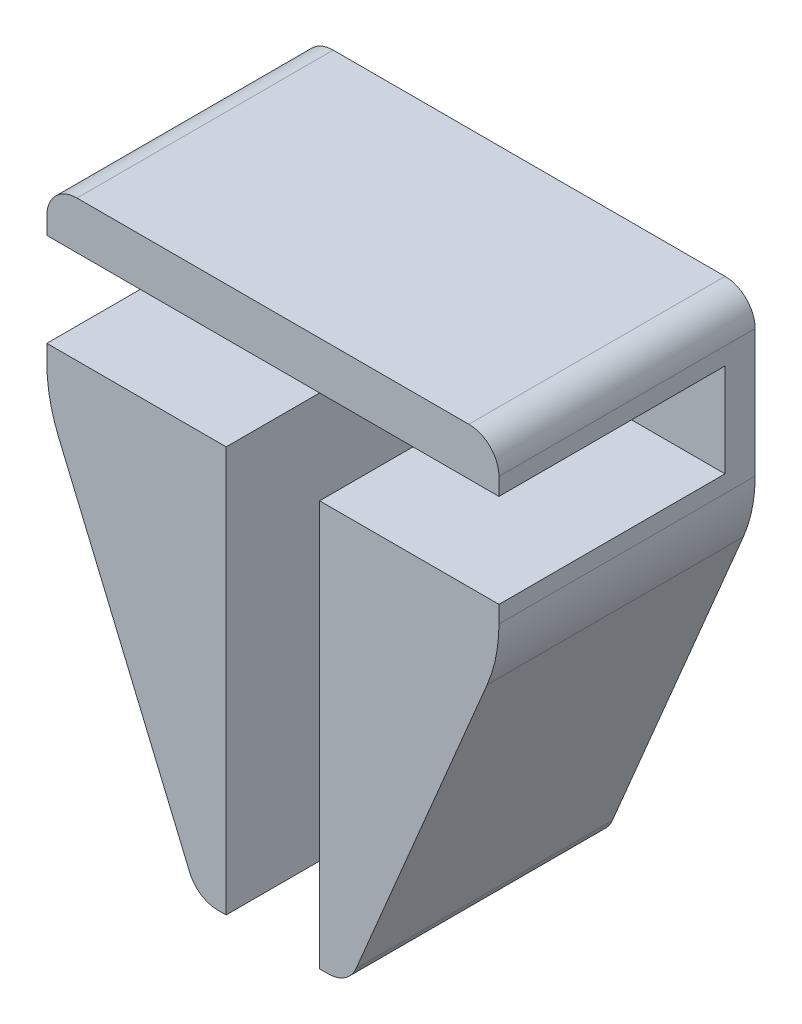
SolidWorks part; units mm, degrees
ref_plane "Płaszczyzna przednia" through (0, 0, 0) normal (0, 0, 1) x (1, 0, 0)
ref_plane "Płaszczyzna górna" through (0, 0, 0) normal (0, 1, 0) x (1, 0, 0)
ref_plane "Płaszczyzna prawa" through (0, 0, 0) normal (1, 0, 0) x (0, 0, -1)
sketch "Szkic1" plane through (0, 0, 0) normal (0, 0, 1) x (1, 0, 0)
  line L0 (-15, 0) -> (15, 0) construction
  line L1 (0, 0) -> (0, -30) construction
  line L2 (-5, -30) -> (5, -30)
  line L3 (15, 6.25) -> (15, -6.25)
  line L4 (-15, 6.25) -> (-15, -6.25)
  line L5 (-15, -6.25) -> (-5, -30)
  line L6 (5, -30) -> (15, -6.25)
  line L7 (15, 6.25) -> (-15, 6.25)
  line L8 (-15, -3.1) -> (-3.1, -3.1)
  line L9 (-15, 3.1) -> (15, 3.1)
  line L10 (-3.1, -3.1) -> (-3.1, -30)
  line L11 (3.1, -3.1) -> (3.1, -30)
  line L12 (3.1, 0) -> (3.1, -30) construction
  line L13 (3.1, -3.1) -> (15, -3.1)
  line L14 (-15, -3.1) -> (15, -3.1) construction
  line L15 (-3.1, 0) -> (-3.1, -30) construction
  point P4 (0, 0)
  point P10 (0, -30)
  point P13 (15, 0)
  point P15 (-15, 0)
  dimension "D1" = 30
  dimension "D2" = 30
  dimension "D3" = 12.5
  dimension "D4" = 10
  dimension "D5" = 3.1
  dimension "D6" = 3.1
  dimension "D7" = 3.1
  dimension "D8" = 3.1
extrude "Dodanie-wyciągnięcie1" add sketch "Szkic1" along normal blind 15 contours L4 L9 L3 L7 | L10 L8 L4 L5 L2 | L13 L11 L2 L6 L3 region at (-7.5068, -13.2868, 0) region at (7.5068, -13.2868, 0) region at (0, 4.675, 0)
extrude "Dodanie-wyciągnięcie2" add sketch "Szkic1<3>" against normal blind 2 contours L7 L4 L5 L2 L6 L3
sketch "Szkic1<3>" plane through (0, 0, 0) normal (0, 0, 1) x (1, 0, 0) same geometry as "Szkic1"
fillet "Zaokrąglenie1" radius 10 2 edges at (-15, -6.25, 6.5) (15, -6.25, 6.5)
fillet "Zaokrąglenie2" radius 2 4 edges at (-15, 6.25, 6.5) (15, 6.25, 6.5) (-5, -30, 6.5) (5, -30, 6.5)
equation "\"D5@Szkic1\"=\"D6@Szkic1\""
equation "\"D8@Szkic1\"=\"D7@Szkic1\""
equation "\"D7@Szkic1\"=\"D6@Szkic1\""
